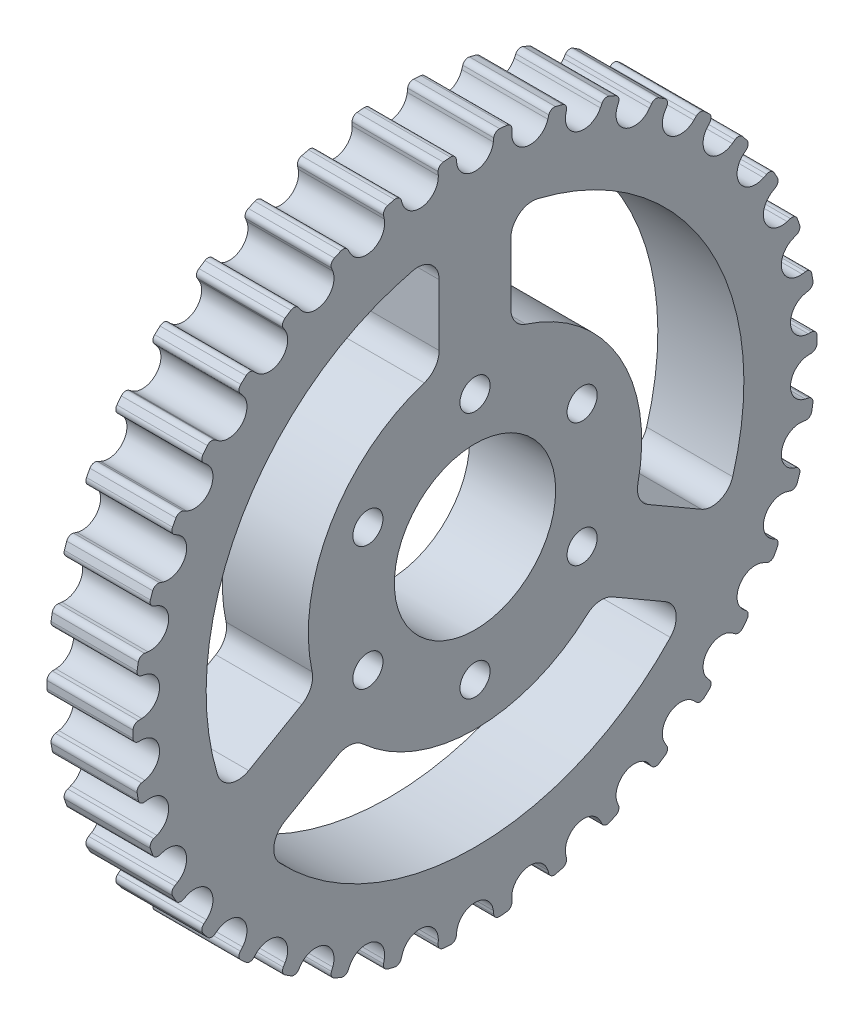
SolidWorks part; units mm, degrees
material "Thornel Mat VMA"
ref_plane "前视基准面" through (0, 0, 0) normal (0, 0, 1) x (1, 0, 0)
ref_plane "上视基准面" through (0, 0, 0) normal (0, 1, 0) x (1, 0, 0)
ref_plane "右视基准面" through (0, 0, 0) normal (1, 0, 0) x (0, 0, -1)
sketch "草图1" plane through (0, 0, 0) normal (0, 0, 1) x (1, 0, 0)
  line L0 (0, 0) -> (64.8368, 0) construction
  line L1 (0, 0) -> (0, 47.699)
  line L2 (0, 47.699) -> (28, 47.699)
  line L3 (28, 47.699) -> (28, 22.1356)
  line L4 (28, 22.1356) -> (20, 22.1356)
  line L5 (20, 22.1356) -> (20, 0)
  line L6 (20, 0) -> (0, 0)
  dimension "L" = 20
  dimension "B" = 28
  dimension "d1" = 44.2712
  dimension "da" = 95.398
revolve "旋转1" add sketch "草图1" angle 360 about L0
ref_axis "基准轴1" through (-1.4, 0, 0) along (1, 0, 0)
sketch "草图6" plane through (0, 0, 0) normal (1, 0, 0) x (0, 0, -1)
  line L0 (0, 0) -> (0, 30.6512) construction
  line L1 (2.6093, 46.8919) -> (2.5508, 46.4158)
  line L2 (4.2172, 47.5122) -> (4.4139, 49.1138)
  line L3 (-4.2172, 47.5122) -> (-4.4139, 49.1138)
  line L4 (-2.6093, 46.8919) -> (-2.5508, 46.4158)
  circle A0 centre (0, 0) radius 47.699 construction
  circle A1 centre (0, 0) radius 44.159 construction
  arc A2 (-2.5508, 46.4158) -> (2.5508, 46.4158) centre (0, 46.729) ccw
  arc A3 (4.4139, 49.1138) -> (-4.4139, 49.1138) centre (0, 0) ccw
  arc A4 (2.6093, 46.8919) -> (3.4397, 47.5748) centre (3.3835, 46.7968) cw
  arc A5 (3.4397, 47.5748) -> (4.2172, 47.5122) centre (0, 0) cw
  arc A6 (-3.4397, 47.5748) -> (-4.2172, 47.5122) centre (0, 0) ccw
  arc A7 (-2.6093, 46.8919) -> (-3.4397, 47.5748) centre (-3.3835, 46.7968) ccw
  point P7 (0, 5.35)
  point P8 (0, 27.1112)
  point P15 (2.699, 47.6226)
  dimension "D1" = 88.318
  dimension "ra" = 0.78
  dimension "rf" = 2.57
  dimension "hg" = 3.54
  dimension "D3" = 0.78
  dimension "D4" = 1.6136
  dimension "angle" = 14
  dimension "bw" = 5.35
extrude "切除-拉伸2" cut sketch "草图6" along normal up to next
pattern_circular "阵列(圆周)3" count 38 over 360 about axis through (-1.4, 0, 0) along (1, 0, 0) of "切除-拉伸2"
sketch "草图8" plane through (28, 0, 0) normal (1, 0, 0) x (0, 0, -1)
  circle A0 centre (0, 0) radius 49
  dimension "D1" = 98
extrude "切除-拉伸4" cut sketch "草图8" against normal offset from surface (16 mm away) 12 up to face at (0, 0, 0)
sketch "草图10" plane through (12, 0, 0) normal (1, 0, 0) x (0, 0, -1)
  line L0 (0, 13.5) -> (0, 0) construction
  line L1 (0, 0) -> (10.5222, 6.075) construction
  line L2 (0, 18) -> (0, 37.5) construction
  line L3 (5, 17.2916) -> (5, 37.1652)
  line L4 (-5, 17.2916) -> (-5, 37.1652)
  line L5 (-5, 18) -> (-5, 37.5) construction
  line L6 (5, 18) -> (5, 37.5) construction
  line L7 (17.475, -4.3157) -> (34.686, -14.2525)
  line L8 (12.475, -12.9759) -> (29.686, -22.9127)
  line L9 (-12.475, -12.9759) -> (-29.686, -22.9127)
  line L10 (-17.475, -4.3157) -> (-34.686, -14.2525)
  circle A0 centre (0, 0) radius 9.15
  circle A1 centre (0, 0) radius 12.15 construction
  circle A2 centre (0, 0) radius 13.5 construction
  circle A3 centre (0, 13.5) radius 1.6
  circle A4 centre (10.5222, 6.075) radius 2.05
  circle A5 centre (11.6913, -6.75) radius 1.6
  circle A6 centre (0, -12.15) radius 2.05
  circle A7 centre (-11.6913, -6.75) radius 1.6
  circle A8 centre (-10.5222, 6.075) radius 2.05
  circle A9 centre (0, 0) radius 18
  circle A10 centre (0, 0) radius 37.5
  point P20 (0, 0)
  point P41 (0, 0)
  dimension "D1" = 24.3
  dimension "D2" = 27
  dimension "D3" = 60
  dimension "D4" = 3.2
  dimension "D5" = 4.1
  dimension "D6" = 3
  dimension "D8" = 36
  dimension "D9" = 75
  dimension "D10" = 5
  dimension "D11" = 5
  dimension "D7" = 3
  dimension "D12" = 3
sketch "草图11" plane through (12, 0, 0) normal (1, 0, 0) x (0, 0, -1)
  line L0 (0, 23.25) -> (0, 37.5) construction
  line L1 (5, 22.706) -> (5, 37.5)
  line L2 (-5, 22.706) -> (-5, 37.5)
  line L3 (-5, 23.25) -> (-5, 37.5) construction
  line L4 (5, 23.25) -> (5, 37.5) construction
  line L5 (17.164, -15.6831) -> (29.976, -23.0801)
  line L6 (22.164, -7.0229) -> (34.976, -14.4199)
  line L7 (-22.164, -7.0229) -> (-34.976, -14.4199)
  line L8 (-17.164, -15.6831) -> (-29.976, -23.0801)
  circle A0 centre (0, 0) radius 17.25 construction
  circle A1 centre (0, 17.25) radius 2.1
  circle A2 centre (14.9389, 8.625) radius 2.1
  circle A3 centre (14.9389, -8.625) radius 2.1
  circle A4 centre (0, -17.25) radius 2.1
  circle A5 centre (-14.9389, -8.625) radius 2.1
  circle A6 centre (-14.9389, 8.625) radius 2.1
  circle A7 centre (0, 0) radius 11.25
  circle A8 centre (0, 0) radius 23.25
  circle A9 centre (0, 0) radius 37.5
  point P18 (0, 0)
  point P25 (24.027, -9.4926)
  point P29 (0, 0)
  point P38 (0, 0)
  dimension "D1" = 34.5
  dimension "D2" = 6
  dimension "D3" = 4.2
  dimension "D4" = 6
  dimension "D5" = 6
  dimension "D6" = 75
  dimension "D7" = 5
  dimension "D8" = 5
  dimension "D9" = 3
extrude "切除-拉伸5" cut sketch "草图11" against normal blind 20 contours A7 | L2 A9 L7 A8 | L6 A9 L1 A8 | L8 A9 L5 A8 | A1 | A6 | A5 | A2 | A3 | A4 region at (12, 13.5684, -23.5012) region at (12, 13.5684, 23.5012) region at (12, -27.1368, 0) region at (12, 0, 0)
fillet "圆角1" radius 3 12 edges at (6, -15.6831, -17.164) (6, -22.9127, -29.686) (6, -22.9127, 29.686) (6, -15.6831, 17.164) (6, 37.1652, -5) (6, -14.2525, -34.686) (6, -7.0229, -22.164) (6, -7.0229, 22.164) (6, -14.2525, 34.686) (6, 37.1652, 5) (6, 22.706, 5) (6, 22.706, -5)
equation "\"D1@草图6\" = \"da@草图1\"  - \"hg@草图6\" - \"hg@草图6\""
equation "\"D3@草图6\" = \"ra@草图6\""
